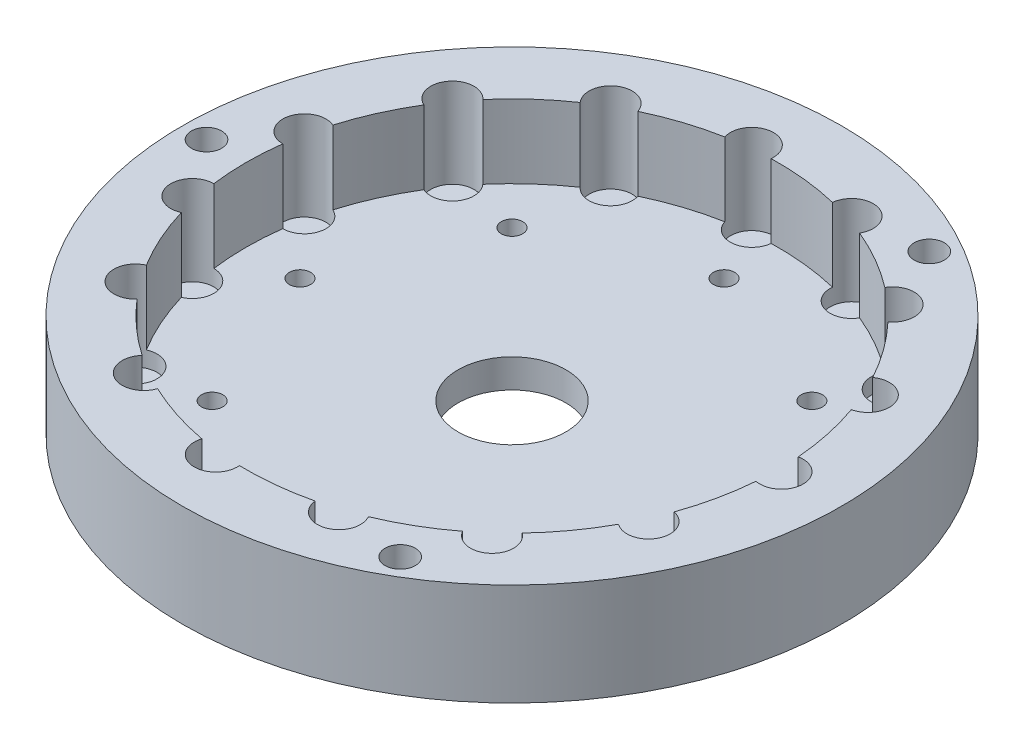
SolidWorks part; units mm, degrees
ref_plane "Front Plane" through (0, 0, 0) normal (0, 0, 1) x (1, 0, 0)
ref_plane "Top Plane" through (0, 0, 0) normal (0, 1, 0) x (1, 0, 0)
ref_plane "Right Plane" through (0, 0, 0) normal (1, 0, 0) x (0, 0, -1)
sketch "Sketch1" plane through (0, 0, 0) normal (0, 1, 0) x (1, 0, 0)
  line L0 (0, 0) -> (-42.5, 0) construction
  circle A0 centre (0, 0) radius 7.5
  circle A1 centre (0, 0) radius 45.85
  circle A2 centre (0, 0) radius 37.5 construction
  circle A3 centre (37.5, 0) radius 3
  circle A4 centre (34.258, 15.2526) radius 3
  circle A5 centre (25.0924, 27.8679) radius 3
  circle A6 centre (11.5881, 35.6646) radius 3
  circle A7 centre (-3.9198, 37.2946) radius 3
  circle A8 centre (-18.75, 32.476) radius 3
  circle A9 centre (-30.3381, 22.0419) radius 3
  circle A10 centre (-36.6805, 7.7967) radius 3
  circle A11 centre (-36.6805, -7.7967) radius 3
  circle A12 centre (-30.3381, -22.0419) radius 3
  circle A13 centre (-18.75, -32.476) radius 3
  circle A14 centre (-3.9198, -37.2946) radius 3
  circle A15 centre (11.5881, -35.6646) radius 3
  circle A16 centre (25.0924, -27.8679) radius 3
  circle A17 centre (34.258, -15.2526) radius 3
  circle A19 centre (0, 0) radius 29.5 construction
  circle A20 centre (29.5, 0) radius 1.48
  circle A21 centre (20.8597, -20.8597) radius 1.48
  circle A22 centre (0, -29.5) radius 1.48
  circle A23 centre (-20.8597, -20.8597) radius 1.48
  circle A24 centre (-29.5, 0) radius 1.48
  circle A25 centre (-20.8597, 20.8597) radius 1.48
  circle A26 centre (0, 29.5) radius 1.48
  circle A27 centre (20.8597, 20.8597) radius 1.48
  arc A28 (36.8833, 2.9359) -> (34.8888, 12.3197) centre (0, 0) ccw
  arc A29 (34.8888, -12.3197) -> (36.8833, -2.9359) centre (0, 0) ccw
  arc A30 (26.8616, -25.4451) -> (32.5004, -17.6839) centre (0, 0) ccw
  arc A31 (14.1898, -34.1709) -> (22.4979, -29.3742) centre (0, 0) ccw
  arc A32 (-0.9355, -36.9882) -> (8.6053, -35.9854) centre (0, 0) ccw
  arc A33 (-15.8991, -33.4099) -> (-6.7752, -36.3744) centre (0, 0) ccw
  arc A34 (-28.1135, -24.0547) -> (-20.9843, -30.4739) centre (0, 0) ccw
  arc A35 (-35.4669, -10.5403) -> (-31.5649, -19.3043) centre (0, 0) ccw
  arc A36 (-36.6878, 4.7967) -> (-36.6878, -4.7967) centre (0, 0) ccw
  arc A37 (-31.5649, 19.3043) -> (-35.4669, 10.5403) centre (0, 0) ccw
  arc A38 (-20.9843, 30.4739) -> (-28.1135, 24.0547) centre (0, 0) ccw
  arc A39 (-6.7752, 36.3744) -> (-15.8991, 33.4099) centre (0, 0) ccw
  arc A40 (8.6053, 35.9854) -> (-0.9355, 36.9882) centre (0, 0) ccw
  arc A41 (22.4979, 29.3742) -> (14.1898, 34.1709) centre (0, 0) ccw
  arc A42 (32.5004, 17.6839) -> (26.8616, 25.4451) centre (0, 0) ccw
  circle A43 centre (-42.5, 0) radius 2.1
  circle A44 centre (21.25, 36.8061) radius 2.1
  circle A45 centre (21.25, -36.8061) radius 2.1
  point P38 (0, 0)
  point P57 (0, 0)
  point P58 (19.4454, -57.9788)
  point P87 (0, 0)
  point P88 (0, 0)
  point P92 (0, 0)
  dimension "D2" = 15
  dimension "D3" = 75
  dimension "D4" = 91.7
  dimension "D5" = 6
  dimension "D8" = 2.96
  dimension "D9" = 59
  dimension "D6" = 37
  dimension "D12" = 4.2
  dimension "D11" = 42.5
  dimension "D1" = 15
  dimension "D7" = 8
  dimension "D10" = 15
  dimension "D13" = 3
extrude "Boss-Extrude1" add sketch "Sketch1" against normal blind 4 contours A4 A42 A5 A41 A6 A40 A7 A39 A8 A38 A9 A37 A10 A36 A11 A35 A12 A34 A13 A33 A14 A32 A15 A31 A16 A30 A17 A29 A3 A28 A0 A20 A21 A22 A23 A24 A25 A26 A27 | A3 | A17 | A4 | A5 | A6 | A7 | A8 | A9 | A10 | A11 | A12 | A13 | A14 | A15 | A16 | A1 A42 A4 A28 A3 A29 A17 A30 A16 A31 A15 A32 A14 A33 A13 A34 A12 A35 A11 A36 A10 A37 A9 A38 A8 A39 A7 A40 A6 A41 A5 | A22 | A23 | A24 | A25 | A26 | A27 | A20 | A21 region at (-45.7203, 0, 0) region at (37.5, 0, 0) region at (33.4543, 0, 0) region at (34.258, 0, -15.2526) region at (34.258, 0, 15.2526) region at (25.0924, 0, -27.8679) region at (25.0924, 0, 27.8679) region at (11.5881, 0, -35.6646) region at (11.5881, 0, 35.6646) region at (-3.9198, 0, -37.2946) region at (-3.9198, 0, 37.2946) region at (-18.75, 0, -32.476) region at (-18.75, 0, 32.476) region at (-30.3381, 0, -22.0419) region at (-30.3381, 0, 22.0419) region at (-36.6805, 0, -7.7967) region at (-36.6805, 0, 7.7967) region at (29.5, 0, 0) region at (20.8597, 0, 20.8597) region at (0, 0, 29.5) region at (-20.8597, 0, 20.8597) region at (-29.5, 0, 0) region at (-20.8597, 0, -20.8597) region at (0, 0, -29.5) region at (20.8597, 0, -20.8597)
extrude "Cut-Extrude1" cut sketch "Sketch1<6>" against normal blind 2.22 contours A24 | A25 | A26 | A27 | A20 | A21 | A22 | A23 | A10 | A11 | A9 | A12 | A13 | A14 | A15 | A16 | A17 | A3 | A4 | A5 | A6 | A7 | A8 region at (37.5, 0, 0) region at (34.258, 0, -15.2526) region at (34.258, 0, 15.2526) region at (25.0924, 0, -27.8679) region at (25.0924, 0, 27.8679) region at (11.5881, 0, -35.6646) region at (11.5881, 0, 35.6646) region at (-3.9198, 0, -37.2946) region at (-3.9198, 0, 37.2946) region at (-18.75, 0, -32.476) region at (-18.75, 0, 32.476) region at (-30.3381, 0, -22.0419) region at (-30.3381, 0, 22.0419) region at (-36.6805, 0, -7.7967) region at (-36.6805, 0, 7.7967) region at (29.5, 0, 0) region at (20.8597, 0, 20.8597) region at (0, 0, 29.5) region at (-20.8597, 0, 20.8597) region at (-29.5, 0, 0) region at (-20.8597, 0, -20.8597) region at (0, 0, -29.5) region at (20.8597, 0, -20.8597)
sketch "Sketch1<6>" plane through (0, 0, 0) normal (0, 1, 0) x (1, 0, 0) same geometry as "Sketch1"
extrude "Boss-Extrude2" add sketch "Sketch1<7>" along normal blind 10.22 contours A1 A42 A4 A28 A3 A29 A17 A30 A16 A31 A15 A32 A14 A33 A13 A34 A12 A35 A11 A36 A10 A37 A9 A38 A8 A39 A7 A40 A6 A41 A5 region at (-45.7203, 0, 0)
sketch "Sketch1<7>" plane through (0, 0, 0) normal (0, 1, 0) x (1, 0, 0) same geometry as "Sketch1"
equation "\"bearing_21_OD\"= 21mm"
equation "\"D2@Sketch1\"=\"bearing_15_OD\"+\"bearing_21_outer_clearance\""
equation "\"pin_cirlce_diameter\"= 75mm"
equation "\"D3@Sketch1\"=\"pin_cirlce_diameter\""
equation "\"pin_diam\"= 6mm"
equation "\"D5@Sketch1\"=\"pin_diam\""
equation "\"gear_thickness\"= 4mm"
equation "\"ball_bearing_diam\"= 2.96mm"
equation "\"bearing_21_outer_clearance\"= 0mm'change this"
equation "\"bearing_15_OD\"= 15mm"
equation "\"bearing_15_outer_clearance\"= 0mm'change this"
equation "\"D8@Sketch1\"=\"ball_bearing_diam\""
equation "\"D1@Cut-Extrude1\"=\"ball_bearing_diam\"*0.75"
equation "\"thrust_bearing_thickness\"= 5mm'measure this irl and change"
equation "\"D1@Boss-Extrude2\"=\"ball_bearing_diam\"*0.75mm+2*\"gear_thickness\""
